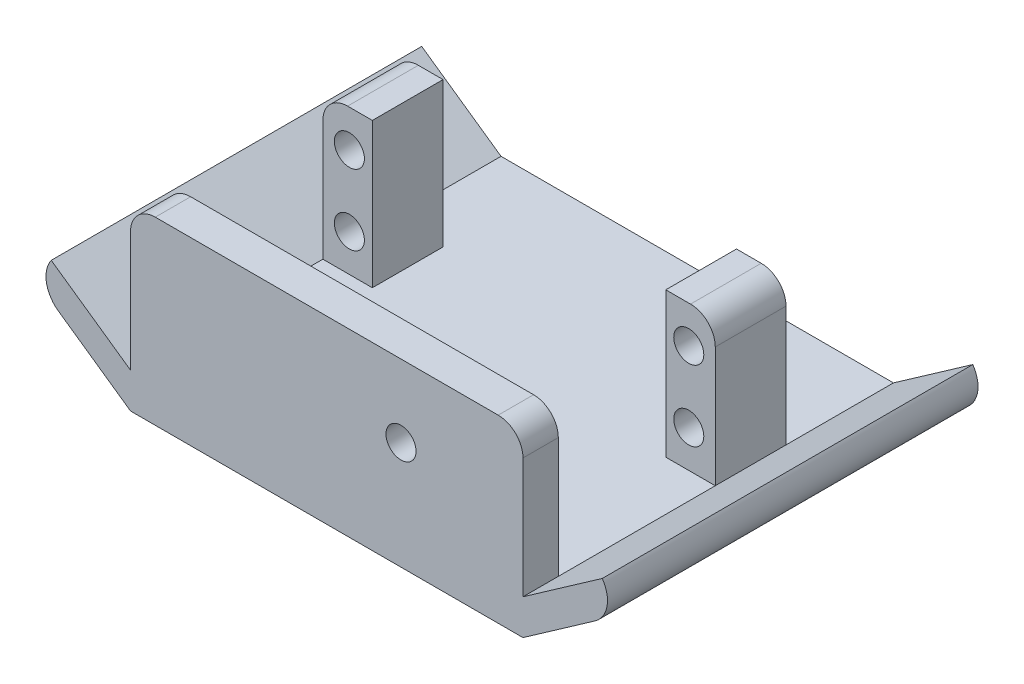
SolidWorks part; units mm, degrees
ref_plane "Front" through (0, 0, 0) normal (0, 0, 1) x (1, 0, 0)
ref_plane "Top" through (0, 0, 0) normal (0, 1, 0) x (1, 0, 0)
ref_plane "Right" through (0, 0, 0) normal (1, 0, 0) x (0, 0, -1)
sketch "Sketch1" plane through (0, 0, 0) normal (0, 1, 0) x (1, 0, 0)
  line L1 (0, 0) -> (55.5, 0)
  line L2 (0, 0) -> (0, 40.4)
  line L3 (0, 40.4) -> (55.5, 40.4)
  line L4 (55.5, 0) -> (55.5, 40.4)
  dimension "D1" = 55.5
  dimension "D2" = 40.4
extrude "base" add sketch "Sketch1" along normal blind 5
sketch "Sketch2" plane through (0, 0, -40.4) normal (0, 0, -1) x (-1, 0, 0)
  line L1 (0, 5) -> (0, 0) construction
  line L2 (-55.5, 0) -> (0, 0)
  line L3 (-55.5, 0) -> (-55.5, 25.5)
  line L4 (-55.5, 25.5) -> (0, 25.5)
  line L5 (0, 0) -> (0, 25.5)
  line L6 (-55.5, 5) -> (0, 5) construction
  dimension "D1" = 20.5
extrude "wall" add sketch "Sketch2" against normal blind 5
ref_plane "Plane1" through (0, 0, -8.2) normal (0, 0, 1) x (1, 0, 0)
sketch "Sketch3" plane through (0, 0, -8.2) normal (0, 0, 1) x (1, 0, 0)
  line L0 (0, 5) -> (55.5, 5) construction
  line L1 (0, 25.5) -> (7, 25.5)
  line L2 (0, 25.5) -> (0, 5)
  line L3 (0, 5) -> (7, 5)
  line L4 (7, 25.5) -> (7, 5)
  line L5 (27.75, 5) -> (27.75, 25.5) construction
  line L6 (55.5, 5) -> (0, 5) construction
  line L7 (0, 25.5) -> (55.5, 25.5) construction
  line L8 (55.5, 5) -> (48.5, 5)
  line L9 (48.5, 25.5) -> (48.5, 5)
  line L10 (55.5, 25.5) -> (48.5, 25.5)
  line L11 (55.5, 25.5) -> (55.5, 5)
  dimension "D1" = 7
extrude "mountingTabs" add sketch "Sketch3" along normal blind 5
sketch "Sketch4" plane through (0, 0, 0) normal (0, 0, 1) x (1, 0, 0)
  line L0 (27.75, 0) -> (27.75, 25.5) construction
  line L1 (0, 0) -> (55.5, 0) construction
  line L2 (0, 25.5) -> (55.5, 25.5) construction
  line L3 (0, 0) -> (-10.2089, 7.1483)
  line L4 (0, 5) -> (-11.2182, 12.8551)
  line L5 (0, 5) -> (0, 0)
  line L6 (55.5, 5) -> (66.7182, 12.8551)
  line L7 (55.5, 5) -> (55.5, 0)
  line L8 (55.5, 0) -> (65.7089, 7.1483)
  arc A0 (-11.2182, 12.8551) -> (-10.2089, 7.1483) centre (-7.8572, 10.5069) ccw
  arc A1 (66.7182, 12.8551) -> (65.7089, 7.1483) centre (63.3572, 10.5069) cw
  dimension "D1" = 145
  dimension "D2" = 12.4627
  dimension "D3" = 13.6949
extrude "lips" add sketch "Sketch4" against normal up to surface (40.4 mm away) up to face at (27.75, 12.75, -40.4)
sketch "Sketch5" plane through (0, 0, -3.2) normal (0, 0, 1) x (1, 0, 0)
  line L0 (27.75, 0) -> (27.75, 25.5) construction
  line L3 (0, 15.25) -> (55.5, 15.25) construction
  line L4 (0, 25.5) -> (0, 5) construction
  line L5 (55.5, 5) -> (55.5, 25.5) construction
  line L6 (7, 25.5) -> (0, 25.5) construction
  line L7 (0, 0) -> (55.5, 0) construction
  line L8 (0, 25.5) -> (55.5, 25.5) construction
  circle A0 centre (3.75, 20.25) radius 2.125
  circle A1 centre (3.75, 10.25) radius 2.125
  circle A4 centre (51.75, 10.25) radius 2.125
  circle A5 centre (51.75, 20.25) radius 2.125
  dimension "D1" = 4.25
  dimension "D2" = 5.25
  dimension "D3" = 3.75
extrude "mountingHoles" cut sketch "Sketch5" against normal blind 5
fillet "fillets" radius 3.5 4 edges at (55.5, 25.5, -37.9) (55.5, 25.5, -5.7) (0, 25.5, -37.9) (0, 25.5, -5.7)
sketch "Sketch6" plane through (0, 0, -35.4) normal (0, 0, 1) x (1, 0, 0)
  line L0 (3.5, 25.5) -> (52, 25.5) construction
  line L1 (55.5, 5) -> (55.5, 22) construction
  circle A0 centre (38.25, 15.25) radius 2.125
  dimension "D1" = 4.25
  dimension "D2" = 10.25
  dimension "D3" = 17.25
extrude "throughHole" cut sketch "Sketch6" against normal blind 5
ref_plane "Plane2" through (0, 0, 0) normal (0, 0, 1) x (1, 0, 0)
mirror "Mirror3" about plane through (0, 0, 0) normal (0, 0, 1) of "fillets", "throughHole", "mountingHoles", "lips", "mountingTabs", "wall", "base"
sketch "Sketch7" plane through (0, 0, 0) normal (0, 0, 1) x (1, 0, 0)
  line L1 (-26.7687, 48.7867) -> (77.7481, 48.7867)
  line L2 (-26.7687, 48.7867) -> (-26.7687, -17.5413)
  line L3 (-26.7687, -17.5413) -> (77.7481, -17.5413)
  line L4 (77.7481, 48.7867) -> (77.7481, -17.5413)
extrude "Cut-Extrude1" cut sketch "Sketch7" against normal blind 73
sketch "Sketch8" plane through (0, 0, 8.2) normal (0, 0, 1) x (1, 0, 0)
  line L4 (7, 25.5) -> (3.5, 25.5)
  line L5 (0, 22) -> (0, 5)
  line L6 (0, 5) -> (7, 5)
  line L7 (7, 5) -> (7, 25.5)
  line L8 (7, 25.5) -> (3.5, 25.5)
  line L9 (0, 22) -> (0, 5)
  line L10 (0, 5) -> (7, 5)
  line L11 (7, 5) -> (7, 25.5)
  line L12 (55.5, 5) -> (55.5, 22)
  line L13 (52, 25.5) -> (48.5, 25.5)
  line L14 (48.5, 25.5) -> (48.5, 5)
  line L15 (48.5, 5) -> (55.5, 5)
  line L16 (55.5, 5) -> (55.5, 22)
  line L17 (52, 25.5) -> (48.5, 25.5)
  line L18 (48.5, 25.5) -> (48.5, 5)
  line L19 (48.5, 5) -> (55.5, 5)
  circle A0 centre (3.75, 20.25) radius 2.125 construction
  arc A1 (3.5, 25.5) -> (0, 22) centre (3.5, 22) ccw
  arc A2 (3.5, 25.5) -> (0, 22) centre (3.5, 22) ccw
  arc A3 (55.5, 22) -> (52, 25.5) centre (52, 22) ccw
  arc A4 (55.5, 22) -> (52, 25.5) centre (52, 22) ccw
  circle A5 centre (3.75, 20.25) radius 2.125
  circle A6 centre (3.75, 10.25) radius 2.125 construction
  circle A7 centre (3.75, 10.25) radius 2.125
  circle A8 centre (51.75, 20.25) radius 2.125 construction
  circle A9 centre (51.75, 20.25) radius 2.125
  circle A10 centre (51.75, 10.25) radius 2.125 construction
  circle A11 centre (51.75, 10.25) radius 2.125
  dimension "D1" = 0
  dimension "D2" = 0
extrude "Boss-Extrude1" add sketch "Sketch8" along normal blind 5
sketch "Sketch9" plane through (0, 0, 0) normal (0, 0, -1) x (-1, 0, 0)
  line L6 (0, 0) -> (10.2089, 7.1483)
  line L7 (11.2182, 12.8551) -> (0, 5)
  line L8 (0, 5) -> (-55.5, 5)
  line L9 (-55.5, 5) -> (-66.7182, 12.8551)
  line L10 (-65.7089, 7.1483) -> (-55.5, 0)
  line L11 (-55.5, 0) -> (0, 0)
  line L12 (0, 0) -> (10.2089, 7.1483)
  line L13 (11.2182, 12.8551) -> (0, 5)
  line L14 (0, 5) -> (-55.5, 5)
  line L15 (-55.5, 5) -> (-66.7182, 12.8551)
  line L16 (-65.7089, 7.1483) -> (-55.5, 0)
  line L17 (-55.5, 0) -> (0, 0)
  arc A2 (10.2089, 7.1483) -> (11.2182, 12.8551) centre (7.8572, 10.5069) ccw
  arc A3 (-66.7182, 12.8551) -> (-65.7089, 7.1483) centre (-63.3572, 10.5069) ccw
  arc A4 (10.2089, 7.1483) -> (11.2182, 12.8551) centre (7.8572, 10.5069) ccw
  arc A5 (-66.7182, 12.8551) -> (-65.7089, 7.1483) centre (-63.3572, 10.5069) ccw
  dimension "D1" = 0
extrude "Boss-Extrude2" add sketch "Sketch9" along normal blind 12
